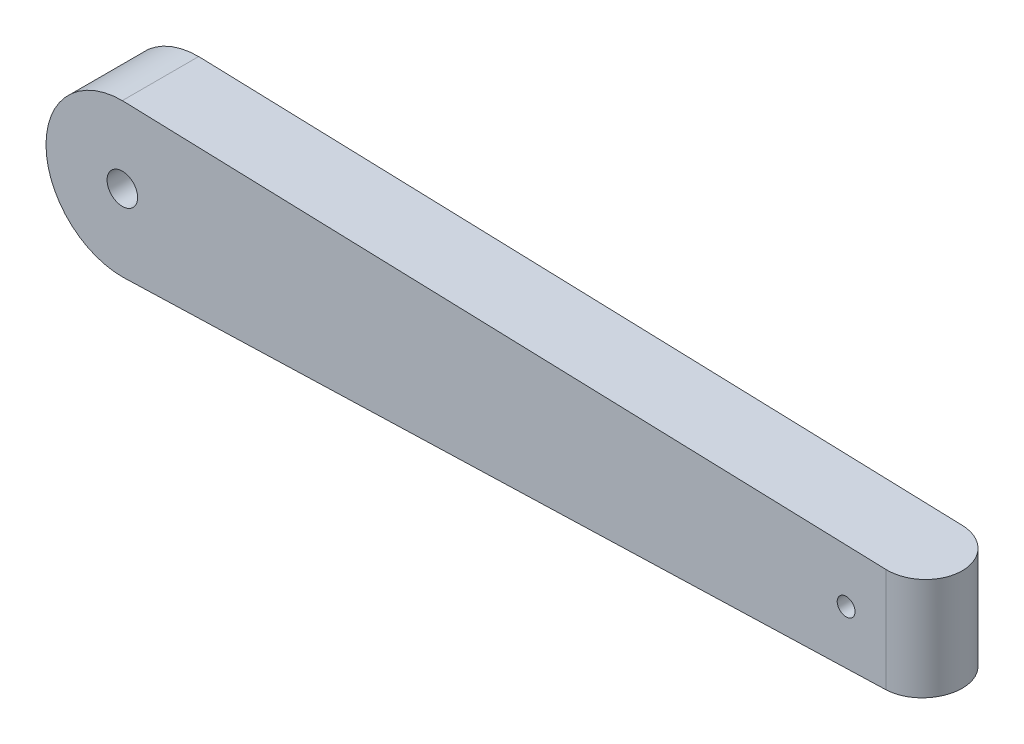
SolidWorks part; units mm, degrees
ref_plane "Front Plane" through (0, 0, 0) normal (0, 0, 1) x (1, 0, 0)
ref_plane "Top Plane" through (0, 0, 0) normal (0, 1, 0) x (1, 0, 0)
ref_plane "Right Plane" through (0, 0, 0) normal (1, 0, 0) x (0, 0, -1)
sketch "Sketch1" plane through (0, 0, 0) normal (0, 0, 1) x (1, 0, 0)
  line L0 (0, 0) -> (157.5, 0) construction
  line L1 (157.5, -10) -> (157.5, 10)
  line L2 (0, 15) -> (157.5, 10)
  line L3 (0, -15) -> (157.5, -10)
  arc A0 (0, -15) -> (0, 15) centre (0, 0) cw
  dimension "D1" = 15
  dimension "D2" = 157.5
  dimension "D3" = 10
extrude "Boss-Extrude2" add sketch "Sketch1" along normal blind 15
fillet "Fillet4" 2 edges at (157.5, 0, 15) (157.5, 0, 0) type full round first side face at (75, 0, 15) second side face at (75, 0, 0) middle face at (157.5, 0, 7.5)
sketch "Sketch2" plane through (0, 0, 15) normal (0, 0, 1) x (1, 0, 0)
  circle A0 centre (142.1971, 0) radius 1.75
  dimension "D1" = 3.5
extrude "Cut-Extrude1" cut sketch "Sketch2" against normal blind 32
sketch "Sketch3" plane through (0, 0, 15) normal (0, 0, 1) x (1, 0, 0)
  circle A0 centre (0, 0) radius 3
  dimension "D1" = 6
extrude "Cut-Extrude2" cut sketch "Sketch3" against normal blind 47
